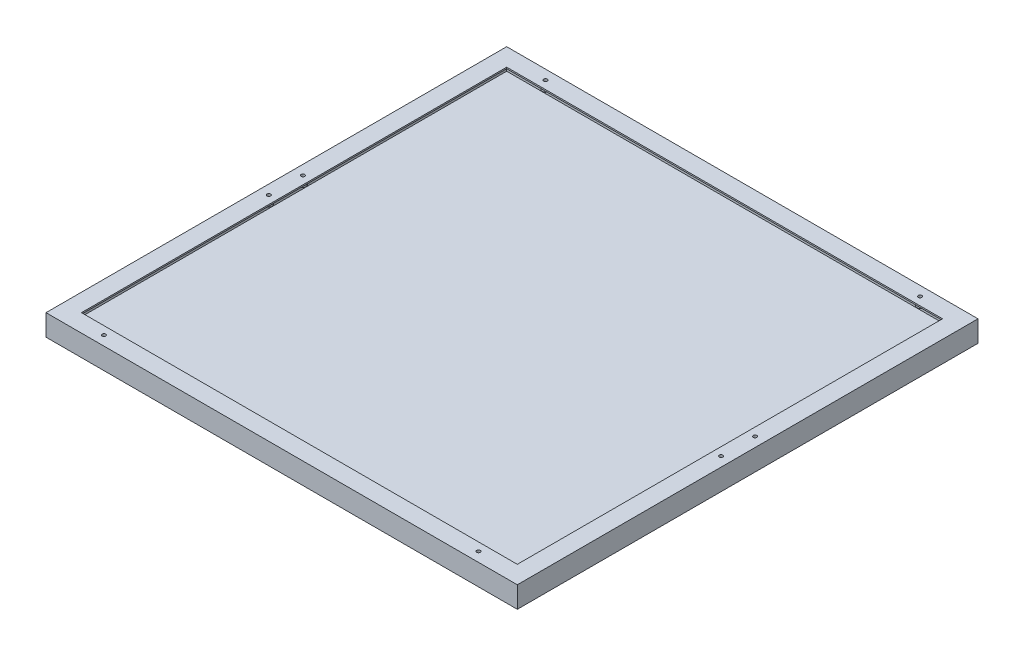
SolidWorks part; units mm, degrees
material "6061-T6 (SS)"
ref_plane "Front" through (0, 0, 0) normal (0, 0, 1) x (1, 0, 0)
ref_plane "Top" through (0, 0, 0) normal (0, 1, 0) x (1, 0, 0)
ref_plane "Right" through (0, 0, 0) normal (1, 0, 0) x (0, 0, -1)
sketch "Sketch1" plane through (0, 0, 0) normal (0, 1, 0) x (1, 0, 0)
  line L1 (0, 0) -> (665, 0)
  line L2 (0, 0) -> (0, 650)
  line L3 (0, 650) -> (665, 650)
  line L4 (665, 0) -> (665, 650)
  dimension "D1" = 665
  dimension "D2" = 650
extrude "Boss-Extrude1" add sketch "Sketch1" against normal blind 30
hole_wizard "#8 (0.199) Diameter Hole1" positions "Sketch3" profile "Sketch2" hole size "#8" standard "ANSI Inch"
sketch "Sketch3" plane through (0, 0, 0) normal (0, 1, 0) x (1, 0, 0)
  line L0 (0, 650) -> (0, 0) construction
  line L1 (0, 0) -> (665, 0) construction
  line L3 (332.5, 650) -> (332.5, 0) construction
  line L4 (665, 650) -> (0, 650) construction
  line L6 (0, 325) -> (665, 325) construction
  line L7 (665, 0) -> (665, 650) construction
  point P10 (68.25, 13.5)
  point P12 (13.5, 301)
  point P43 (596.75, 13.5)
  point P44 (651.5, 301)
  point P47 (651.5, 349)
  point P48 (596.75, 636.5)
  point P49 (68.25, 636.5)
  point P50 (13.5, 349)
  dimension "D1" = 13.5
  dimension "D4" = 301
  dimension "D5" = 13.5
  dimension "D6" = 68.25
sketch "Sketch2" plane through (68.25, 0, -13.5) normal (1, 0, 0) x (0, 0, 1)
  line L0 (0, 0) -> (0, 9.65)
  line L1 (0, 9.65) -> (2.5273, 9.65)
  line L2 (2.5273, 9.65) -> (2.5273, 0)
  line L5 (2.5273, 0) -> (0, 0)
  line L10 (0, 9.65) -> (-2.5273, 9.65) construction
  line L11 (0, -6.35) -> (0, 107.95) construction
  dimension "Hole Dia." = 5.0546
  dimension "Hole Depth" = 9.65
  dimension "Drill Angle" = 180
sketch "Sketch4" plane through (0, 0, 0) normal (0, 1, 0) x (1, 0, 0)
  line L0 (0, 650) -> (0, 0) construction
  line L1 (25, 625) -> (640, 625)
  line L2 (25, 625) -> (25, 25)
  line L3 (25, 25) -> (640, 25)
  line L4 (640, 625) -> (640, 25)
  line L5 (665, 650) -> (0, 650) construction
  line L6 (665, 0) -> (665, 650) construction
  line L7 (0, 0) -> (665, 0) construction
  dimension "D1" = 25
  dimension "D2" = 25
  dimension "D3" = 25
  dimension "D4" = 25
extrude "Cut-Extrude1" cut sketch "Sketch4" against normal blind 20
shell "Shell" thickness 2 removed face at (25, -10, -325) removed face at (332.5, -10, -25) removed face at (640, -10, -325) removed face at (332.5, -10, -625) removed face at (332.5, -20, -325)
